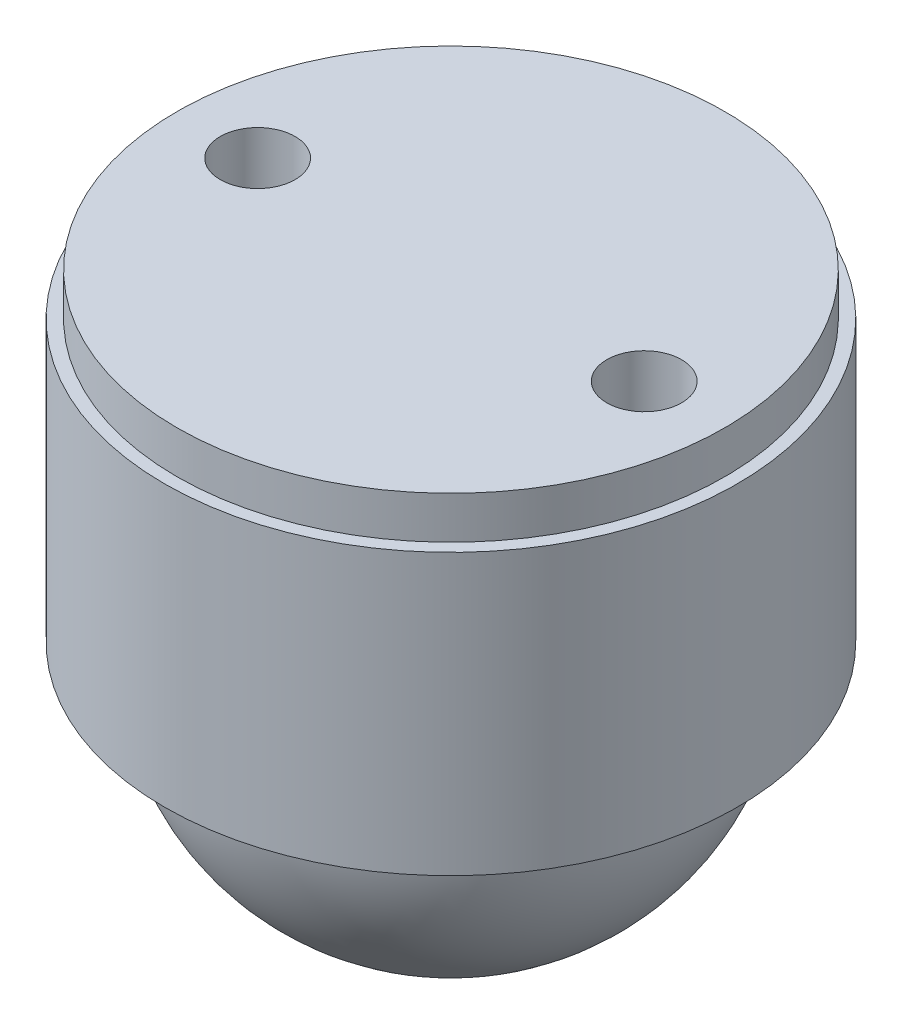
SolidWorks part; units mm, degrees
ref_plane "Front Plane" through (0, 0, 0) normal (0, 0, 1) x (1, 0, 0)
ref_plane "Top Plane" through (0, 0, 0) normal (0, 1, 0) x (1, 0, 0)
ref_plane "Right Plane" through (0, 0, 0) normal (1, 0, 0) x (0, 0, -1)
sketch "Sketch1" plane through (0, 0, 0) normal (0, 1, 0) x (1, 0, 0)
  line L0 (0, 9.525) -> (0, -9.525)
  arc A0 (0, -9.525) -> (0, 9.525) centre (0, 0) ccw
  dimension "D1" = 9.525
  dimension "D2" = 19.05
revolve "Revolve1" add sketch "Sketch1" angle 360 about L0
sketch "Sketch2" plane through (0, 0, 0) normal (0, 1, 0) x (1, 0, 0)
  circle A0 centre (0, 0) radius 11.475
  dimension "D1" = 22.95
extrude "Boss-Extrude1" add sketch "Sketch2" along normal blind 11.225
sketch "Sketch5" plane through (0, 11.225, 0) normal (0, 1, 0) x (1, 0, 0)
  circle A0 centre (0, 0) radius 10.98
  dimension "D1" = 21.96
extrude "Boss-Extrude3" add sketch "Sketch5" along normal blind 1.7
sketch "Sketch6" plane through (0, 12.925, 0) normal (0, 1, 0) x (1, 0, 0)
  circle A0 centre (7.747, 0) radius 1.5
  circle A1 centre (-7.747, 0) radius 1.5
  circle A2 centre (0, 0) radius 10.98 construction
  point P5 (0, 0)
  dimension "D3" = 3
  dimension "D4" = 3
  dimension "D1" = 15.494
  dimension "D2" = 7.747
  dimension "D5" = 7.747
  dimension "D6" = 7.747
extrude "Cut-Extrude4" cut sketch "Sketch6" against normal blind 5
